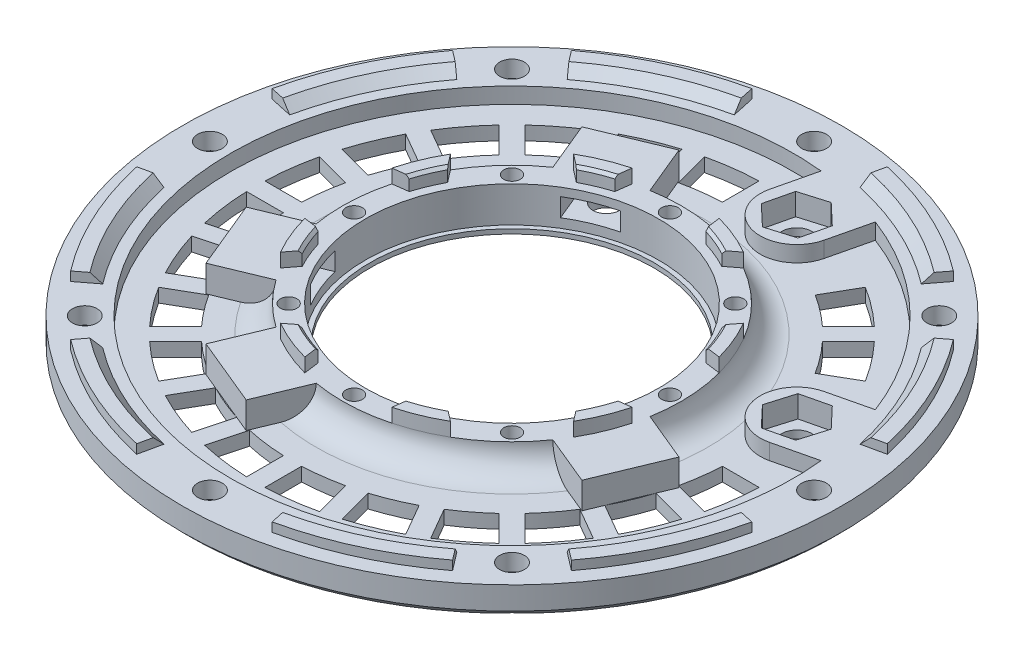
SolidWorks part; units mm, degrees
ref_plane "Front Plane" through (0, 0, 0) normal (0, 0, 1) x (1, 0, 0)
ref_plane "Top Plane" through (0, 0, 0) normal (0, 1, 0) x (1, 0, 0)
ref_plane "Right Plane" through (0, 0, 0) normal (1, 0, 0) x (0, 0, -1)
sketch "Sketch1" plane through (0, 0, 0) normal (0, 1, 0) x (1, 0, 0)
  circle A0 centre (0, 0) radius 16.025
  circle A1 centre (0, 0) radius 36
  dimension "D1" = 32.05
  dimension "D2" = 72
extrude "Boss-Extrude1" add sketch "Sketch1" along normal blind 1
sketch "Sketch2" plane through (0, 0, 0) normal (0, -1, 0) x (1, 0, 0)
  circle A0 centre (0, 0) radius 17.25 construction
  circle A1 centre (0, 0) radius 18.5 construction
  circle A2 centre (0, 0) radius 18.5
  circle A3 centre (0, 0) radius 16.025 construction
  circle A4 centre (0, 0) radius 16.025
  arc A5 (-1.2, 18.461) -> (-4.705, 17.8917) centre (0, 0) ccw construction
  point P3 (0, -17.25)
extrude "Boss-Extrude2" add sketch "Sketch2" against normal offset from surface (3.9 mm away) 3.9 up to face at (0, 0, 36)
fillet "Fillet1" radius 2.9 1 edges at (0, 1, 18.5)
sketch "Sketch4" plane through (0, 0, 0) normal (0, 1, 0) x (1, 0, 0)
  circle A0 centre (0, 0) radius 15.525
  circle A1 centre (0, 0) radius 36
  circle A2 centre (0, 0) radius 36
  circle A3 centre (0, 0) radius 16.025 construction
  dimension "D2" = 0.5
  dimension "D1" = 0
extrude "Boss-Extrude3" add sketch "Sketch4" against normal blind 0.5
sketch "Sketch5" plane through (0, 1, 0) normal (0, 1, 0) x (1, 0, 0)
  line L0 (27.99, -0.75) -> (19.9859, -0.75) construction
  line L1 (19.9859, 0.75) -> (27.99, 0.75) construction
  line L2 (27.99, -0.75) -> (19.9859, -0.75) construction
  line L3 (19.9859, 0.75) -> (27.99, 0.75) construction
  line L4 (0, 0) -> (36, 0) construction
  line L5 (0, 0) -> (34.7733, 9.3175) construction
  line L6 (34.7733, 9.3175) -> (36, 0) construction
  line L7 (0, 0) -> (35.3867, 4.6587) construction
  line L8 (27.99, 1) -> (23.9792, 1)
  line L9 (27.295, 6.2784) -> (23.4209, 5.2403)
  line L10 (27.99, -1) -> (23.9792, -1)
  line L11 (27.295, -6.2784) -> (23.4209, -5.2403)
  line L12 (26.7774, -8.2103) -> (22.9033, -7.1722)
  line L13 (24.74, -13.129) -> (21.2666, -11.1236)
  line L14 (23.74, -14.861) -> (20.2666, -12.8556)
  line L15 (20.499, -19.0848) -> (17.6629, -16.2487)
  line L16 (19.0848, -20.499) -> (16.2487, -17.6629)
  line L17 (14.861, -23.74) -> (12.8556, -20.2666)
  line L18 (13.129, -24.74) -> (11.1236, -21.2666)
  line L19 (8.2103, -26.7774) -> (7.1722, -22.9033)
  line L20 (6.2784, -27.295) -> (5.2403, -23.4209)
  line L21 (1, -27.99) -> (1, -23.9792)
  line L22 (-1, -27.99) -> (-1, -23.9792)
  line L23 (-6.2784, -27.295) -> (-5.2403, -23.4209)
  line L24 (-8.2103, -26.7774) -> (-7.1722, -22.9033)
  line L25 (-13.129, -24.74) -> (-11.1236, -21.2666)
  line L26 (-14.861, -23.74) -> (-12.8556, -20.2666)
  line L27 (-19.0848, -20.499) -> (-16.2487, -17.6629)
  line L28 (-20.499, -19.0848) -> (-17.6629, -16.2487)
  line L29 (-23.74, -14.861) -> (-20.2666, -12.8556)
  line L30 (-24.74, -13.129) -> (-21.2666, -11.1236)
  line L31 (-26.7774, -8.2103) -> (-22.9033, -7.1722)
  line L32 (-27.295, -6.2784) -> (-23.4209, -5.2403)
  line L33 (-27.99, -1) -> (-23.9792, -1)
  line L34 (-27.99, 1) -> (-23.9792, 1)
  line L35 (-27.295, 6.2784) -> (-23.4209, 5.2403)
  line L36 (-26.7774, 8.2103) -> (-22.9033, 7.1722)
  line L37 (-24.74, 13.129) -> (-21.2666, 11.1236)
  line L38 (-23.74, 14.861) -> (-20.2666, 12.8556)
  line L39 (-20.499, 19.0848) -> (-17.6629, 16.2487)
  line L40 (-19.0848, 20.499) -> (-16.2487, 17.6629)
  line L41 (-14.861, 23.74) -> (-12.8556, 20.2666)
  line L42 (-13.129, 24.74) -> (-11.1236, 21.2666)
  line L43 (-8.2103, 26.7774) -> (-7.1722, 22.9033)
  line L44 (-6.2784, 27.295) -> (-5.2403, 23.4209)
  line L45 (-1, 27.99) -> (-1, 23.9792)
  line L46 (1, 27.99) -> (1, 23.9792)
  line L47 (6.2784, 27.295) -> (5.2403, 23.4209)
  line L48 (8.2103, 26.7774) -> (7.1722, 22.9033)
  line L49 (13.129, 24.74) -> (11.1236, 21.2666)
  line L50 (14.861, 23.74) -> (12.8556, 20.2666)
  line L51 (19.0848, 20.499) -> (16.2487, 17.6629)
  line L52 (20.499, 19.0848) -> (17.6629, 16.2487)
  line L53 (23.74, 14.861) -> (20.2666, 12.8556)
  line L54 (24.74, 13.129) -> (21.2666, 11.1236)
  line L55 (26.7774, 8.2103) -> (22.9033, 7.1722)
  line L56 (0, 0) -> (23.9792, 1) construction
  circle A0 centre (0, 0) radius 24 construction
  circle A2 centre (0, 0) radius 36 construction
  arc A3 (23.9792, 1) -> (23.4209, 5.2403) centre (0, 0) ccw
  arc A4 (27.99, 1) -> (27.295, 6.2784) centre (0, 0) ccw
  arc A5 (27.295, -6.2784) -> (27.99, -1) centre (0, 0) ccw
  arc A6 (23.4209, -5.2403) -> (23.9792, -1) centre (0, 0) ccw
  arc A7 (24.74, -13.129) -> (26.7774, -8.2103) centre (0, 0) ccw
  arc A8 (21.2666, -11.1236) -> (22.9033, -7.1722) centre (0, 0) ccw
  arc A9 (20.499, -19.0848) -> (23.74, -14.861) centre (0, 0) ccw
  arc A10 (17.6629, -16.2487) -> (20.2666, -12.8556) centre (0, 0) ccw
  arc A11 (14.861, -23.74) -> (19.0848, -20.499) centre (0, 0) ccw
  arc A12 (12.8556, -20.2666) -> (16.2487, -17.6629) centre (0, 0) ccw
  arc A13 (8.2103, -26.7774) -> (13.129, -24.74) centre (0, 0) ccw
  arc A14 (7.1722, -22.9033) -> (11.1236, -21.2666) centre (0, 0) ccw
  arc A15 (1, -27.99) -> (6.2784, -27.295) centre (0, 0) ccw
  arc A16 (1, -23.9792) -> (5.2403, -23.4209) centre (0, 0) ccw
  arc A17 (-6.2784, -27.295) -> (-1, -27.99) centre (0, 0) ccw
  arc A18 (-5.2403, -23.4209) -> (-1, -23.9792) centre (0, 0) ccw
  arc A19 (-13.129, -24.74) -> (-8.2103, -26.7774) centre (0, 0) ccw
  arc A20 (-11.1236, -21.2666) -> (-7.1722, -22.9033) centre (0, 0) ccw
  arc A21 (-19.0848, -20.499) -> (-14.861, -23.74) centre (0, 0) ccw
  arc A22 (-16.2487, -17.6629) -> (-12.8556, -20.2666) centre (0, 0) ccw
  arc A23 (-23.74, -14.861) -> (-20.499, -19.0848) centre (0, 0) ccw
  arc A24 (-20.2666, -12.8556) -> (-17.6629, -16.2487) centre (0, 0) ccw
  arc A25 (-26.7774, -8.2103) -> (-24.74, -13.129) centre (0, 0) ccw
  arc A26 (-22.9033, -7.1722) -> (-21.2666, -11.1236) centre (0, 0) ccw
  arc A27 (-27.99, -1) -> (-27.295, -6.2784) centre (0, 0) ccw
  arc A28 (-23.9792, -1) -> (-23.4209, -5.2403) centre (0, 0) ccw
  arc A29 (-27.295, 6.2784) -> (-27.99, 1) centre (0, 0) ccw
  arc A30 (-23.4209, 5.2403) -> (-23.9792, 1) centre (0, 0) ccw
  arc A31 (-24.74, 13.129) -> (-26.7774, 8.2103) centre (0, 0) ccw
  arc A32 (-21.2666, 11.1236) -> (-22.9033, 7.1722) centre (0, 0) ccw
  arc A33 (-20.499, 19.0848) -> (-23.74, 14.861) centre (0, 0) ccw
  arc A34 (-17.6629, 16.2487) -> (-20.2666, 12.8556) centre (0, 0) ccw
  arc A35 (-14.861, 23.74) -> (-19.0848, 20.499) centre (0, 0) ccw
  arc A36 (-12.8556, 20.2666) -> (-16.2487, 17.6629) centre (0, 0) ccw
  arc A37 (-8.2103, 26.7774) -> (-13.129, 24.74) centre (0, 0) ccw
  arc A38 (-7.1722, 22.9033) -> (-11.1236, 21.2666) centre (0, 0) ccw
  arc A39 (-1, 27.99) -> (-6.2784, 27.295) centre (0, 0) ccw
  arc A40 (-1, 23.9792) -> (-5.2403, 23.4209) centre (0, 0) ccw
  arc A41 (6.2784, 27.295) -> (1, 27.99) centre (0, 0) ccw
  arc A42 (5.2403, 23.4209) -> (1, 23.9792) centre (0, 0) ccw
  arc A43 (13.129, 24.74) -> (8.2103, 26.7774) centre (0, 0) ccw
  arc A44 (11.1236, 21.2666) -> (7.1722, 22.9033) centre (0, 0) ccw
  arc A45 (19.0848, 20.499) -> (14.861, 23.74) centre (0, 0) ccw
  arc A46 (16.2487, 17.6629) -> (12.8556, 20.2666) centre (0, 0) ccw
  arc A47 (23.74, 14.861) -> (20.499, 19.0848) centre (0, 0) ccw
  arc A48 (20.2666, 12.8556) -> (17.6629, 16.2487) centre (0, 0) ccw
  arc A49 (26.7774, 8.2103) -> (24.74, 13.129) centre (0, 0) ccw
  arc A50 (22.9033, 7.1722) -> (21.2666, 11.1236) centre (0, 0) ccw
  dimension "D1" = 15
  dimension "D2" = 1
  dimension "D4" = 24
  dimension "D3" = 24
extrude "Cut-Extrude1" cut sketch "Sketch5" against normal through all both and the other way through all
sketch "Sketch7" plane through (0, 3.9, 0) normal (0, 1, 0) x (1, 0, 0)
  line L0 (0, 0) -> (0, 17.25) construction
  circle A0 centre (0, 17.25) radius 0.9
  circle A1 centre (12.1976, 12.1976) radius 0.9
  circle A2 centre (17.25, 0) radius 0.9
  circle A3 centre (12.1976, -12.1976) radius 0.9
  circle A4 centre (0, -17.25) radius 0.9
  circle A5 centre (-12.1976, -12.1976) radius 0.9
  circle A6 centre (-17.25, 0) radius 0.9
  circle A7 centre (-12.1976, 12.1976) radius 0.9
  point P21 (0, 0)
  dimension "D1" = 1.8
  dimension "D2" = 8
extrude "Cut-Extrude2" cut sketch "Sketch7" against normal through all
sketch "Sketch8" plane through (0, 1, 0) normal (0, 1, 0) x (1, 0, 0)
  arc A0 (-30.7407, -0.7544) -> (-30.0499, -6.5245) centre (0, 0) ccw construction
  arc A1 (-30.7407, -0.7544) -> (-30.0499, -6.5245) centre (0, 0) ccw construction
  arc A2 (-30.0499, 6.5245) -> (-30.7407, 0.7544) centre (0, 0) ccw construction
  arc A3 (-30.0499, 6.5245) -> (-30.7407, 0.7544) centre (0, 0) ccw construction
  circle A5 centre (0, 0) radius 30.75
  circle A6 centre (0, 0) radius 36 construction
  circle A7 centre (0, 0) radius 36
extrude "Boss-Extrude4" add sketch "Sketch8" along normal blind 1.7378
sketch "Sketch9" plane through (0, 2.7378, 0) normal (0, 1, 0) x (1, 0, 0)
  line L0 (0, 0) -> (-30.0499, 6.5245) construction
  line L1 (0, 0) -> (-30.0499, -6.5245) construction
  line L2 (-30.0499, 6.5245) -> (-30.0499, -6.5245) construction
  line L3 (-27.3707, 21.0023) -> (-23.9989, 18.415) construction
  line L4 (0, 0) -> (0, 36) construction
  line L5 (0, 0) -> (-25.4558, 25.4558) construction
  line L6 (-24.3956, 18.7194) -> (0, 0) construction
  line L7 (-24.3956, 18.7194) -> (-28.5607, 21.9154) construction
  line L8 (-30.0499, 6.5245) -> (-35.1803, 7.6384) construction
  line L9 (-27.3521, 20.862) -> (-25.3687, 19.3401)
  line L10 (-31.2086, 14.47) -> (0, 0) construction
  line L11 (-33.5954, 7.3966) -> (-31.1523, 6.8662)
  line L12 (-7.3966, 33.5954) -> (-6.8662, 31.1523)
  line L13 (-20.862, 27.3521) -> (-19.3401, 25.3687)
  arc A0 (-30.0499, 6.5245) -> (-24.3956, 18.7194) centre (0, 0) cw construction
  arc A1 (-35.1803, 7.6384) -> (-28.5607, 21.9154) centre (0, 0) cw construction
  circle A2 centre (0, 0) radius 36 construction
  circle A3 centre (0, 0) radius 30.75 construction
  arc A4 (-27.2914, 20.9414) -> (-33.6168, 7.2989) centre (0, 0) ccw construction
  arc A5 (-31.1523, 6.8662) -> (-25.3687, 19.3401) centre (0, 0) cw
  arc A6 (-33.5954, 7.3966) -> (-27.3521, 20.862) centre (0, 0) cw
  circle A7 centre (0, 0) radius 36 construction
  arc A8 (-6.8662, 31.1523) -> (-19.3401, 25.3687) centre (0, 0) ccw
  arc A9 (-7.3966, 33.5954) -> (-20.862, 27.3521) centre (0, 0) ccw
  dimension "D2" = 0.1
  dimension "D3" = 45
  dimension "D4" = 0.1
  dimension "D1" = 2.5
extrude "Boss-Extrude5" add sketch "Sketch9" along normal blind 1
ref_axis "Axis1" through (0, -0.72, 0) along (0, 1, 0)
pattern_circular "CirPattern1" count 4 over 360 about axis through (0, -0.72, 0) along (0, 1, 0) of "Boss-Extrude5"
chamfer "Chamfer1" distance 1 angle 45 8 edges at (-28.9406, 3.7378, -13.4184) (-13.4184, 3.7378, -28.9406) (13.4184, 3.7378, -28.9406) (28.9406, 3.7378, -13.4184) (28.9406, 3.7378, 13.4184) (13.4184, 3.7378, 28.9406) (-13.4184, 3.7378, 28.9406) (-28.9406, 3.7378, 13.4184)
sketch "Sketch10" plane through (0, 2.7378, 0) normal (0, 1, 0) x (1, 0, 0)
  line L0 (0, 0) -> (0, 36) construction
  circle A0 centre (0, 0) radius 36 construction
  circle A1 centre (0, 33) radius 1.1 construction
  circle A2 centre (0, 33) radius 1.1
  circle A3 centre (23.3345, 23.3345) radius 1.1
  circle A4 centre (33, 0) radius 1.1
  circle A5 centre (23.3345, -23.3345) radius 1.1
  circle A6 centre (0, -33) radius 1.1
  circle A7 centre (-23.3345, -23.3345) radius 1.1
  circle A8 centre (-33, 0) radius 1.1
  circle A9 centre (-23.3345, 23.3345) radius 1.1
  point P26 (0, 0)
  dimension "D1" = 8
extrude "Cut-Extrude3" cut sketch "Sketch10" against normal through all both and the other way through all
chamfer "Chamfer2" distance 0.75 angle 45 1 edges at (0, -0.5, 36)
hole_wizard "CSK for M2.5 Flat Head Machine Screw1" positions "Sketch11" profile "Sketch12" countersink size "M2.5" standard "ANSI Metric" end condition through all
sketch "Sketch11" plane through (0, -0.5, 0) normal (0, -1, 0) x (-1, 0, 0)
  point P0 (0, -33)
  point P3 (23.3345, -23.3345)
  point P6 (33, 0)
  point P9 (23.3345, 23.3345)
  point P12 (0, 33)
  point P15 (-23.3345, 23.3345)
  point P18 (-33, 0)
  point P21 (-23.3345, -23.3345)
sketch "Sketch12" plane through (0, -0.5, 33) normal (1, 0, 0) x (0, 0, -1)
  line L0 (0, 0) -> (0, 4.4)
  line L1 (0, 4.4) -> (1.35, 4.4)
  line L2 (1.35, 4.4) -> (1.35, 1.4)
  line L3 (1.35, 1.4) -> (2.75, 0)
  line L5 (2.75, 0) -> (0, 0)
  line L6 (-1.35, 1.4) -> (-2.75, 0) construction
  line L11 (0, -6.35) -> (0, 107.95) construction
  dimension "Thru Hole Dia." = 2.7
  dimension "Thru Hole Depth" = 4.4
  dimension "Near C'Sink Dia." = 5.5
  dimension "Near C'Sink Angle" = 90
sketch "Sketch13" plane through (0, 3.9, 0) normal (0, 1, 0) x (1, 0, 0)
  line L0 (0, 0) -> (-7.0796, 17.0918) construction
  line L1 (0, 0) -> (0, 18.5) construction
  line L2 (-9.2808, 16.0037) -> (-7.9403, 14.9751)
  line L3 (-4.7538, 17.8788) -> (-4.9743, 16.2037)
  line L4 (4.7538, 17.8788) -> (4.9743, 16.2037)
  line L5 (9.2808, 16.0037) -> (7.9403, 14.9751)
  line L6 (16.0037, 9.2808) -> (14.9751, 7.9403)
  line L7 (17.8788, 4.7538) -> (16.2037, 4.9743)
  line L8 (17.8788, -4.7538) -> (16.2037, -4.9743)
  line L9 (16.0037, -9.2808) -> (14.9751, -7.9403)
  line L10 (9.2808, -16.0037) -> (7.9403, -14.9751)
  line L11 (4.7538, -17.8788) -> (4.9743, -16.2037)
  line L12 (-4.7538, -17.8788) -> (-4.9743, -16.2037)
  line L13 (-9.2808, -16.0037) -> (-7.9403, -14.9751)
  line L14 (-16.0037, -9.2808) -> (-14.9751, -7.9403)
  line L15 (-17.8788, -4.7538) -> (-16.2037, -4.9743)
  line L16 (-17.8788, 4.7538) -> (-16.2037, 4.9743)
  line L17 (-16.0037, 9.2808) -> (-14.9751, 7.9403)
  circle A0 centre (0, 0) radius 18.5 construction
  arc A1 (-7.9403, 14.9751) -> (-4.9743, 16.2037) centre (0, 0) cw
  arc A2 (-9.2808, 16.0037) -> (-4.7538, 17.8788) centre (0, 0) cw
  arc A3 (4.9743, 16.2037) -> (7.9403, 14.9751) centre (0, 0) cw
  arc A4 (4.7538, 17.8788) -> (9.2808, 16.0037) centre (0, 0) cw
  arc A5 (14.9751, 7.9403) -> (16.2037, 4.9743) centre (0, 0) cw
  arc A6 (16.0037, 9.2808) -> (17.8788, 4.7538) centre (0, 0) cw
  arc A7 (16.2037, -4.9743) -> (14.9751, -7.9403) centre (0, 0) cw
  arc A8 (17.8788, -4.7538) -> (16.0037, -9.2808) centre (0, 0) cw
  arc A9 (7.9403, -14.9751) -> (4.9743, -16.2037) centre (0, 0) cw
  arc A10 (9.2808, -16.0037) -> (4.7538, -17.8788) centre (0, 0) cw
  arc A11 (-4.9743, -16.2037) -> (-7.9403, -14.9751) centre (0, 0) cw
  arc A12 (-4.7538, -17.8788) -> (-9.2808, -16.0037) centre (0, 0) cw
  arc A13 (-14.9751, -7.9403) -> (-16.2037, -4.9743) centre (0, 0) cw
  arc A14 (-16.0037, -9.2808) -> (-17.8788, -4.7538) centre (0, 0) cw
  arc A15 (-16.2037, 4.9743) -> (-14.9751, 7.9403) centre (0, 0) cw
  arc A16 (-17.8788, 4.7538) -> (-16.0037, 9.2808) centre (0, 0) cw
  point P12 (-6.4865, 15.6598)
  point P20 (6.4865, 15.6598)
  point P25 (15.6598, 6.4865)
  point P30 (15.6598, -6.4865)
  point P35 (6.4865, -15.6598)
  point P40 (-6.4865, -15.6598)
  point P45 (-15.6598, -6.4865)
  point P50 (-15.6598, 6.4865)
  point P51 (0, 0)
  dimension "D1" = 22.5
  dimension "D2" = 30
  dimension "D3" = 1.55
  dimension "D4" = 4.9
  dimension "D5" = 8
extrude "Boss-Extrude6" add sketch "Sketch13" along normal blind 1.5
chamfer "Chamfer3" distance 0.3 angle 45 8 edges at (-15.6598, 5.4, -6.4865) (-15.6598, 5.4, 6.4865) (-6.4865, 5.4, 15.6598) (6.4865, 5.4, 15.6598) (15.6598, 5.4, 6.4865) (15.6598, 5.4, -6.4865) (6.4865, 5.4, -15.6598) (-6.4865, 5.4, -15.6598)
sketch "Sketch14" plane through (0, -0.5, 0) normal (0, -1, 0) x (1, 0, 0)
  line L0 (0, 0) -> (25.4558, -25.4558) construction
  line L1 (0, 0) -> (0, -36) construction
  line L6 (0, 0) -> (-22.1731, 9.1844) construction
  line L7 (0, 0) -> (-9.1844, -22.1731) construction
  circle A0 centre (0, 0) radius 36 construction
  circle A1 centre (0, 0) radius 16.025 construction
  arc A5 (-21.2666, 11.1236) -> (-22.9033, 7.1722) centre (0, 0) ccw construction
  circle A6 centre (-17.5768, 7.2806) radius 1.45
  circle A7 centre (-17.5768, 7.2806) radius 4.975 construction
  arc A8 (-11.1236, -21.2666) -> (-7.1722, -22.9033) centre (0, 0) ccw construction
  circle A9 centre (-7.2806, -17.5768) radius 1.45
  circle A10 centre (-7.2806, -17.5768) radius 4.975 construction
  circle A11 centre (17.5768, 7.2806) radius 1.45
  circle A12 centre (-7.2806, 17.5768) radius 1.45
  point P25 (-14.8052, 6.1325)
  point P28 (-16.2372, 6.7257)
  dimension "D2" = 2.9
  dimension "D3" = 3
  dimension "D1" = 45
sketch "Sketch15" plane through (0, 1, 0) normal (0, 1, 0) x (1, 0, 0)
  line L0 (-9.8825, 13.2519) -> (-12.8979, 20.5316)
  line L1 (-9.8825, 13.2519) -> (-2.3825, 16.3585)
  line L2 (-12.8979, 20.5316) -> (-5.3979, 23.6382)
  line L3 (-2.3825, 16.3585) -> (-5.3979, 23.6382)
  line L4 (-9.8825, 13.2519) -> (-5.3979, 23.6382) construction
  line L5 (-12.8979, 20.5316) -> (-2.3825, 16.3585) construction
  line L6 (0, 0) -> (-9.1844, 22.1731) construction
  line L7 (2.3825, 16.3585) -> (5.3979, 23.6382) [skipped]
  line L8 (2.3825, 16.3585) -> (9.8825, 13.2519) [skipped]
  line L9 (5.3979, 23.6382) -> (12.8979, 20.5316) [skipped]
  line L10 (9.8825, 13.2519) -> (12.8979, 20.5316) [skipped]
  line L11 (2.3825, 16.3585) -> (12.8979, 20.5316) construction
  line L12 (5.3979, 23.6382) -> (9.8825, 13.2519) construction
  line L13 (13.2519, 9.8825) -> (20.5316, 12.8979) [skipped]
  line L14 (13.2519, 9.8825) -> (16.3585, 2.3825) [skipped]
  line L15 (20.5316, 12.8979) -> (23.6382, 5.3979) [skipped]
  line L16 (16.3585, 2.3825) -> (23.6382, 5.3979) [skipped]
  line L17 (13.2519, 9.8825) -> (23.6382, 5.3979) construction
  line L18 (20.5316, 12.8979) -> (16.3585, 2.3825) construction
  line L19 (16.3585, -2.3825) -> (23.6382, -5.3979)
  line L20 (16.3585, -2.3825) -> (13.2519, -9.8825)
  line L21 (23.6382, -5.3979) -> (20.5316, -12.8979)
  line L22 (13.2519, -9.8825) -> (20.5316, -12.8979)
  line L23 (16.3585, -2.3825) -> (20.5316, -12.8979) construction
  line L24 (23.6382, -5.3979) -> (13.2519, -9.8825) construction
  line L25 (9.8825, -13.2519) -> (12.8979, -20.5316) [skipped]
  line L26 (9.8825, -13.2519) -> (2.3825, -16.3585) [skipped]
  line L27 (12.8979, -20.5316) -> (5.3979, -23.6382) [skipped]
  line L28 (2.3825, -16.3585) -> (5.3979, -23.6382) [skipped]
  line L29 (9.8825, -13.2519) -> (5.3979, -23.6382) construction
  line L30 (12.8979, -20.5316) -> (2.3825, -16.3585) construction
  line L31 (-2.3825, -16.3585) -> (-5.3979, -23.6382)
  line L32 (-2.3825, -16.3585) -> (-9.8825, -13.2519)
  line L33 (-5.3979, -23.6382) -> (-12.8979, -20.5316)
  line L34 (-9.8825, -13.2519) -> (-12.8979, -20.5316)
  line L35 (-2.3825, -16.3585) -> (-12.8979, -20.5316) construction
  line L36 (-5.3979, -23.6382) -> (-9.8825, -13.2519) construction
  line L37 (-13.2519, -9.8825) -> (-20.5316, -12.8979)
  line L38 (-13.2519, -9.8825) -> (-16.3585, -2.3825)
  line L39 (-20.5316, -12.8979) -> (-23.6382, -5.3979)
  line L40 (-16.3585, -2.3825) -> (-23.6382, -5.3979)
  line L41 (-13.2519, -9.8825) -> (-23.6382, -5.3979) construction
  line L42 (-20.5316, -12.8979) -> (-16.3585, -2.3825) construction
  line L43 (-16.3585, 2.3825) -> (-23.6382, 5.3979) [skipped]
  line L44 (-16.3585, 2.3825) -> (-13.2519, 9.8825) [skipped]
  line L45 (-23.6382, 5.3979) -> (-20.5316, 12.8979) [skipped]
  line L46 (-13.2519, 9.8825) -> (-20.5316, 12.8979) [skipped]
  line L47 (-16.3585, 2.3825) -> (-20.5316, 12.8979) construction
  line L48 (-23.6382, 5.3979) -> (-13.2519, 9.8825) construction
  line L49 (0, 0) -> (-9.1844, 22.1731) construction
  arc A1 (-7.1722, 22.9033) -> (-11.1236, 21.2666) centre (0, 0) ccw construction
  circle A2 centre (0, 0) radius 16.025 construction
  point P1 (-7.6402, 18.445)
  point P9 (7.6402, 18.445)
  point P18 (18.445, 7.6402)
  point P23 (18.445, -7.6402)
  point P28 (7.6402, -18.445)
  point P33 (-7.6402, -18.445)
  point P38 (-18.445, -7.6402)
  point P43 (-18.445, 7.6402)
  point P48 (0, 0)
  dimension "D1" = 7.5
  dimension "D2" = 8
extrude "Boss-Extrude7" add sketch "Sketch15" along normal up to surface (2.9 mm away) up to face at (0, 3.9, -16.35)
extrude "Cut-Extrude4" cut sketch "Sketch14" against normal blind 3.5
sketch "Sketch16" plane through (0, -0.5, 0) normal (0, -1, 0) x (1, 0, 0)
  line L0 (0, 0) -> (23.3345, -23.3345) construction
  line L1 (10.1026, 7.7782) -> (22.348, -8.1266) construction
  line L2 (0, 0) -> (0, -17.25) construction
  line L3 (0, 0) -> (10.1026, 7.7782) construction
  line L4 (18.6021, 8.3059) -> (13.454, 13.454) construction
  line L5 (0, 0) -> (13.454, 13.454) construction
  line L6 (25.1212, -5.9915) -> (27.5961, -3.5166) construction
  line L7 (27.5961, -3.5166) -> (12.0398, 12.0398) construction
  circle A0 centre (0, 0) radius 12.75 construction
  circle A1 centre (25.1212, -5.9915) radius 1.65
  circle A2 centre (25.1212, -5.9915) radius 3.5 construction
  circle A3 centre (17.5768, 7.2806) radius 1.45 construction
  circle A4 centre (5.9915, -25.1212) radius 1.65
  dimension "D1" = 25.5
  dimension "D2" = 3.3
  dimension "D3" = 7
  dimension "D4" = 2
  dimension "D5" = 22
sketch "Sketch17" plane through (0, -0.5, 0) normal (0, -1, 0) x (1, 0, 0)
  line L0 (24.74, -13.129) -> (21.2666, -11.1236) construction
  line L1 (24.74, -13.129) -> (21.2666, -11.1236)
  line L2 (0, 0) -> (12.1976, -12.1976) construction
  line L3 (13.129, -24.74) -> (11.1236, -21.2666)
  arc A0 (21.2666, -11.1236) -> (22.9033, -7.1722) centre (0, 0) ccw construction
  arc A1 (24.74, -13.129) -> (26.7774, -8.2103) centre (0, 0) ccw construction
  arc A4 (21.2666, -11.1236) -> (21.5701, -10.5228) centre (0, 0) ccw
  arc A5 (24.74, -13.129) -> (25.4284, -11.7403) centre (0, 0) ccw
  arc A8 (25.4284, -11.7403) -> (21.5701, -10.5228) centre (25.1212, -5.9915) ccw
  arc A9 (11.7403, -25.4284) -> (10.5228, -21.5701) centre (5.9915, -25.1212) cw
  arc A10 (13.129, -24.74) -> (11.7403, -25.4284) centre (0, 0) cw
  arc A11 (11.1236, -21.2666) -> (10.5228, -21.5701) centre (0, 0) cw
extrude "Boss-Extrude8" add sketch "Sketch17" against normal up to surface (1.5 mm away) up to face at (25.7264, 1, -3.3869)
sketch "Sketch18" plane through (0, 1, 0) normal (0, 1, 0) x (1, 0, 0)
  line L0 (0, 0) -> (25.1212, 5.9915) construction
  line L1 (24.1933, 9.8823) -> (28.7289, 10.9641)
  line L2 (26.0492, 2.1006) -> (30.5849, 3.1823)
  line L3 (0, 0) -> (23.3345, 23.3345) construction
  line L4 (9.8823, 24.1933) -> (10.9641, 28.7289)
  line L5 (2.1006, 26.0492) -> (3.1823, 30.5849)
  arc A0 (24.1933, 9.8823) -> (26.0492, 2.1006) centre (25.1212, 5.9915) ccw
  circle A1 centre (0, 0) radius 30.75 construction
  circle A2 centre (0, 0) radius 30.75 construction
  arc A3 (30.5849, 3.1823) -> (28.7289, 10.9641) centre (0, 0) ccw
  arc A4 (3.1823, 30.5849) -> (10.9641, 28.7289) centre (0, 0) cw
  arc A5 (9.8823, 24.1933) -> (2.1006, 26.0492) centre (5.9915, 25.1212) cw
  circle A6 centre (23.3345, 23.3345) radius 1.1 construction
  dimension "D1" = 8
extrude "Boss-Extrude9" add sketch "Sketch18" along normal up to surface (1.7378 mm away) up to face at (0, 2.7378, 34.35)
extrude "Cut-Extrude5" cut sketch "Sketch16" against normal through all
sketch "Sketch19" plane through (0, 2.7378, 0) normal (0, 1, 0) x (1, 0, 0)
  line L0 (0, 0) -> (25.1212, 5.9915) construction
  line L1 (28.1539, 6.7147) -> (26.0112, 8.9794)
  line L2 (26.0112, 8.9794) -> (22.9785, 8.2561)
  line L3 (22.9785, 8.2561) -> (22.0886, 5.2682)
  line L4 (22.0886, 5.2682) -> (24.2313, 3.0035)
  line L5 (24.2313, 3.0035) -> (27.2639, 3.7268)
  line L6 (27.2639, 3.7268) -> (28.1539, 6.7147)
  line L7 (0, 0) -> (23.3345, 23.3345) construction
  line L8 (3.7268, 27.2639) -> (6.7147, 28.1539)
  line L9 (3.0035, 24.2313) -> (3.7268, 27.2639)
  line L10 (5.2682, 22.0886) -> (3.0035, 24.2313)
  line L11 (8.2561, 22.9785) -> (5.2682, 22.0886)
  line L12 (8.9794, 26.0112) -> (8.2561, 22.9785)
  line L13 (6.7147, 28.1539) -> (8.9794, 26.0112)
  circle A0 centre (25.1212, 5.9915) radius 2.7 construction
  circle A1 centre (23.3345, 23.3345) radius 1.35 construction
  dimension "D1" = 5.4
extrude "Cut-Extrude6" cut sketch "Sketch19" against normal blind 2.4
sketch "Sketch20" plane through (0, 3, 0) normal (0, -1, 0) x (1, 0, 0)
  line L0 (0, 0) -> (-17.5768, 7.2806) construction
  line L5 (-15.2866, 9.0379) -> (-13.6672, 8.3671)
  line L6 (-14.9098, 6.1758) -> (-15.2866, 9.0379) construction
  line L16 (-15.2866, 9.0379) -> (-17.9536, 10.1426)
  line L17 (-17.9536, 10.1426) -> (-20.2438, 8.3853)
  line L18 (-20.2438, 8.3853) -> (-19.867, 5.5232)
  line L19 (-19.867, 5.5232) -> (-17.2, 4.4185)
  line L20 (-17.2, 4.4185) -> (-14.9098, 6.1758) construction
  line L21 (-13.6672, 8.3671) -> (-15.5806, 3.7477)
  line L28 (-15.5806, 3.7477) -> (-17.2, 4.4185)
  line L29 (-8.3671, 13.6672) -> (-9.0379, 15.2866)
  line L30 (-10.1426, 17.9536) -> (-9.0379, 15.2866)
  line L31 (-8.3853, 20.2438) -> (-10.1426, 17.9536)
  line L32 (-5.5232, 19.867) -> (-8.3853, 20.2438)
  line L33 (-4.4185, 17.2) -> (-5.5232, 19.867)
  line L34 (-4.4185, 17.2) -> (-3.7477, 15.5806)
  line L35 (-3.7477, 15.5806) -> (-8.3671, 13.6672)
  line L36 (3.7477, 15.5806) -> (4.4185, 17.2) [skipped]
  line L37 (5.5232, 19.867) -> (4.4185, 17.2) [skipped]
  line L38 (8.3853, 20.2438) -> (5.5232, 19.867) [skipped]
  line L39 (10.1426, 17.9536) -> (8.3853, 20.2438) [skipped]
  line L46 (9.0379, 15.2866) -> (10.1426, 17.9536) [skipped]
  line L47 (9.0379, 15.2866) -> (8.3671, 13.6672) [skipped]
  line L48 (8.3671, 13.6672) -> (3.7477, 15.5806) [skipped]
  line L49 (13.6672, 8.3671) -> (15.2866, 9.0379)
  line L50 (17.9536, 10.1426) -> (15.2866, 9.0379)
  line L51 (20.2438, 8.3853) -> (17.9536, 10.1426)
  line L52 (19.867, 5.5232) -> (20.2438, 8.3853)
  line L53 (17.2, 4.4185) -> (19.867, 5.5232)
  line L54 (17.2, 4.4185) -> (15.5806, 3.7477)
  line L55 (15.5806, 3.7477) -> (13.6672, 8.3671)
  line L56 (15.5806, -3.7477) -> (17.2, -4.4185) [skipped]
  line L57 (19.867, -5.5232) -> (17.2, -4.4185) [skipped]
  line L58 (20.2438, -8.3853) -> (19.867, -5.5232) [skipped]
  line L59 (17.9536, -10.1426) -> (20.2438, -8.3853) [skipped]
  line L60 (15.2866, -9.0379) -> (17.9536, -10.1426) [skipped]
  line L61 (15.2866, -9.0379) -> (13.6672, -8.3671) [skipped]
  line L62 (13.6672, -8.3671) -> (15.5806, -3.7477) [skipped]
  line L63 (8.3671, -13.6672) -> (9.0379, -15.2866) [skipped]
  line L64 (10.1426, -17.9536) -> (9.0379, -15.2866) [skipped]
  line L65 (8.3853, -20.2438) -> (10.1426, -17.9536) [skipped]
  line L66 (5.5232, -19.867) -> (8.3853, -20.2438) [skipped]
  line L67 (4.4185, -17.2) -> (5.5232, -19.867) [skipped]
  line L68 (4.4185, -17.2) -> (3.7477, -15.5806) [skipped]
  line L69 (3.7477, -15.5806) -> (8.3671, -13.6672) [skipped]
  line L70 (-3.7477, -15.5806) -> (-4.4185, -17.2)
  line L71 (-5.5232, -19.867) -> (-4.4185, -17.2)
  line L72 (-8.3853, -20.2438) -> (-5.5232, -19.867)
  line L73 (-10.1426, -17.9536) -> (-8.3853, -20.2438)
  line L74 (-9.0379, -15.2866) -> (-10.1426, -17.9536)
  line L75 (-9.0379, -15.2866) -> (-8.3671, -13.6672)
  line L76 (-8.3671, -13.6672) -> (-3.7477, -15.5806)
  line L77 (-13.6672, -8.3671) -> (-15.2866, -9.0379) [skipped]
  line L78 (-17.9536, -10.1426) -> (-15.2866, -9.0379) [skipped]
  line L79 (-20.2438, -8.3853) -> (-17.9536, -10.1426) [skipped]
  line L80 (-19.867, -5.5232) -> (-20.2438, -8.3853) [skipped]
  line L81 (-17.2, -4.4185) -> (-19.867, -5.5232) [skipped]
  line L82 (-17.2, -4.4185) -> (-15.5806, -3.7477) [skipped]
  line L83 (-15.5806, -3.7477) -> (-13.6672, -8.3671) [skipped]
  circle A1 centre (-17.5768, 7.2806) radius 2.5 construction
  circle A3 centre (0, 0) radius 16.025 construction
  point P57 (0, 0)
  point P69 (0, 0)
  dimension "D1" = 5
extrude "Cut-Extrude7" cut sketch "Sketch20" along normal blind 2
ref_plane "Plane1" through (0.6364, 0, 0.6364) normal (-0.7071, 0, -0.7071) x (-0.7071, 0, 0.7071)
